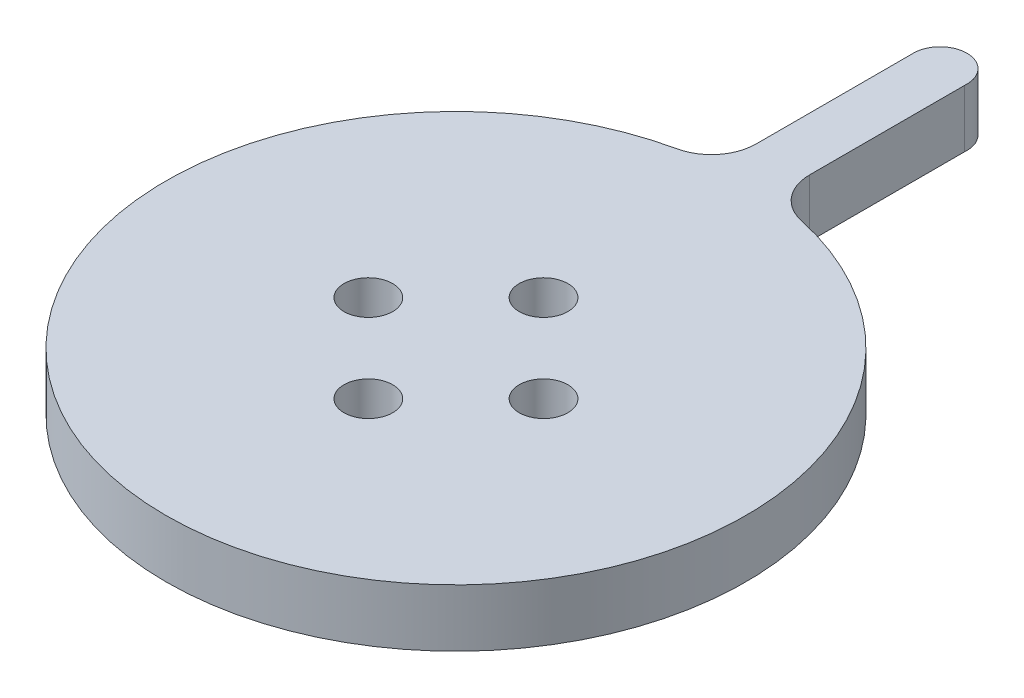
SolidWorks part; units mm, degrees
ref_plane "Front Plane" through (0, 0, 0) normal (0, 0, 1) x (1, 0, 0)
ref_plane "Top Plane" through (0, 0, 0) normal (0, 1, 0) x (1, 0, 0)
ref_plane "Right Plane" through (0, 0, 0) normal (1, 0, 0) x (0, 0, -1)
sketch "Sketch2" plane through (0, 0, 0) normal (0, 1, 0) x (1, 0, 0)
  circle A0 centre (0, 0) radius 32.768
extrude "Boss-Extrude1" add sketch "Sketch2" along normal blind 5
sketch "Sketch3" plane through (0, 0, 0) normal (0, -1, 0) x (1, 0, 0)
  circle A0 centre (0, 0) radius 32.768
  circle A1 centre (0, 0) radius 30.268
extrude "Boss-Extrude2" add sketch "Sketch3" along normal blind 1.5
sketch "Sketch4" plane through (0, 5, 0) normal (0, 1, 0) x (1, 0, 0)
  circle A9 centre (0, 9.8995) radius 2.75
  circle A10 centre (-9.9, 0) radius 2.75
  circle A11 centre (9.9, 0) radius 2.75
  circle A12 centre (0, -9.9) radius 2.75
  dimension "D3" = 9.9
  dimension "D1" = 9.8995
  dimension "D2" = 9.9
  dimension "D4" = 9.9
extrude "Cut-Extrude1" cut sketch "Sketch4" against normal blind 9.8995 contours A12 | A12 | A10 | A9 | A11 region at (0, 5, 9.9)
sketch "Sketch5" plane through (0, 5, 0) normal (0, 1, 0) x (1, 0, 0)
  line L1 (-3.0234, 36.9517) -> (-3.0234, 54.9517)
  line L3 (3.0234, 54.4772) -> (3.0234, 36.9517)
  arc A0 (-7, 32.0116) -> (7, 32.0116) centre (0, 0) cw
  circle A1 centre (0, 0) radius 32.768 construction
  arc A2 (-7, 32.0116) -> (-3.0234, 36.9517) centre (-8.0803, 36.9517) ccw
  arc A3 (7, 32.0116) -> (3.0234, 36.9517) centre (8.0803, 36.9517) cw
  arc A4 (3.0234, 54.4772) -> (-3.0234, 54.9517) centre (0, 54.7144) ccw
  dimension "D1" = 18
extrude "Boss-Extrude3" add sketch "Sketch5" against normal blind 6.5
